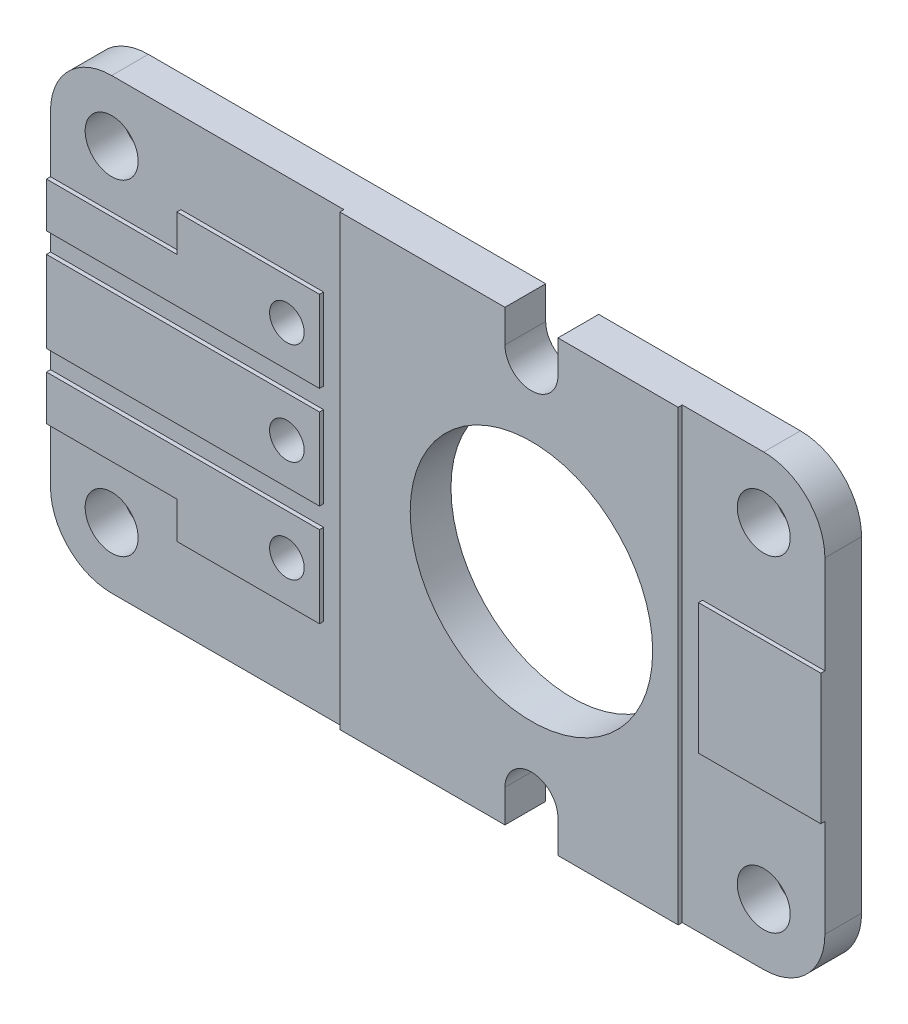
SolidWorks part; units mm, degrees
ref_plane "Спереди" through (0, 0, 0) normal (0, 0, 1) x (1, 0, 0)
ref_plane "Сверху" through (0, 0, 0) normal (0, 1, 0) x (1, 0, 0)
ref_plane "Справа" through (0, 0, 0) normal (1, 0, 0) x (0, 0, -1)
sketch "Model" plane through (0, 0, 0) normal (0, 0, 1) x (1, 0, 0)
  line L0 (1025.0386, -772.2) -> (1025.0386, -762.8) construction
  line L1 (1024.3886, -762.8) -> (1024.3886, -762)
  line L2 (1025.0386, -763.5) -> (1030.6386, -763.5) construction
  line L3 (1025.6886, -762.8) -> (1025.6886, -762)
  line L4 (1025.0386, -763.5) -> (1014.6386, -763.5) construction
  line L5 (1013.1386, -763.5) -> (1013.1386, -771.5)
  line L6 (1025.0386, -767.5) -> (1032.9639, -767.5) construction
  line L7 (1032.1386, -763.5) -> (1032.1386, -771.5)
  line L8 (1014.6386, -762) -> (1030.6386, -762)
  line L9 (1014.6386, -773) -> (1030.6386, -773)
  line L10 (1025.0386, -771.5) -> (1014.6386, -771.5) construction
  line L11 (1025.0386, -771.5) -> (1030.6386, -771.5) construction
  line L12 (1024.3886, -762.8) -> (1024.3886, -762)
  line L13 (1025.6886, -762.8) -> (1025.6886, -762)
  line L14 (1025.6886, -772.2) -> (1025.6886, -773)
  line L15 (1024.3886, -772.2) -> (1024.3886, -773)
  line L16 (1025.6886, -772.2) -> (1025.6886, -773)
  line L17 (1024.3886, -772.2) -> (1024.3886, -773)
  arc A0 (1024.3886, -762.8) -> (1025.6886, -762.8) centre (1025.0386, -762.8) ccw
  arc A1 (1025.0386, -770.5001) -> (1025.0386, -764.5) centre (1025.0386, -767.5001) ccw
  arc A2 (1025.0386, -764.5) -> (1025.0386, -770.5001) centre (1025.0386, -767.5001) ccw
  circle A12 centre (1014.6386, -763.5) radius 1.5
  circle A13 centre (1030.6386, -763.5) radius 1.5
  circle A14 centre (1014.6386, -763.5) radius 0.65
  circle A15 centre (1030.6386, -763.5) radius 0.65
  circle A16 centre (1014.6386, -771.5) radius 0.65
  circle A17 centre (1014.6386, -771.5) radius 1.5
  circle A18 centre (1019.0386, -765) radius 0.4246
  circle A19 centre (1019.0386, -765) radius 0.7246
  circle A20 centre (1019.0378, -767.4991) radius 0.4246
  circle A21 centre (1019.0378, -767.4991) radius 0.7246
  circle A22 centre (1019.0386, -770) radius 0.4246
  circle A23 centre (1019.0386, -770) radius 0.7246
  circle A24 centre (1025.0386, -767.5) radius 2.9746
  circle A25 centre (1025.0386, -767.5) radius 3.4746
  circle A26 centre (1030.6386, -771.5) radius 0.65
  circle A27 centre (1030.6386, -771.5) radius 1.5
  arc A28 (1024.3886, -772.2) -> (1025.6886, -772.2) centre (1025.0386, -772.2) cw
  point P27 (1013.1386, -767.5)
  point P45 (1032.1386, -767.5)
  dimension "D1" = 9.4
  dimension "D2" = 4
  dimension "D3" = 4
extrude "Бобышка-Вытянуть1" add sketch "Model" along normal mid plane 1 contours A25 A23 A21 A19 | A25 A2 A1 | A1 A2 A24 | A23 A22 | A21 A20 | A19 A18 | A27 A26 | A13 A15 | A12 A14 | A17 A16 region at (1025.0386, -763.6696, 0) region at (1015.6693, -762.4694, 0) region at (1031.6693, -762.4694, 0) region at (1014.6386, -770.0425, 0) region at (1031.6693, -772.5307, 0) region at (1022.047, -767.5001, 0) region at (1018.3345, -765, 0) region at (1018.3337, -767.4991, 0) region at (1018.3345, -770, 0) region at (1021.6623, -767.5, 0)
sketch "Эскиз2" plane through (0, 0, 0.5) normal (0, 0, 1) x (1, 0, 0)
  line L2 (1029.2386, -760.837) -> (1034.3761, -760.837)
  line L3 (1034.3761, -760.837) -> (1034.3761, -770.1)
  line L4 (1025.0386, -767.5) -> (1032.1386, -767.5)
  line L5 (1034.3761, -774.163) -> (1034.3761, -770.1)
  line L6 (1029.2386, -774.163) -> (1034.3761, -774.163)
  line L9 (1014.6386, -764.9) -> (1011.6405, -764.9)
  line L10 (1016.0386, -760.614) -> (1011.6405, -760.614)
  line L11 (1011.6405, -760.614) -> (1011.6405, -764.9)
  line L12 (1019.8386, -766) -> (1019.8386, -764)
  line L13 (1019.8386, -760.837) -> (1020.3386, -760.837)
  line L14 (1020.3386, -760.837) -> (1020.3386, -764)
  line L15 (1019.8386, -760.837) -> (1016.0386, -760.614)
  line L16 (1016.3386, -766.5) -> (1011.6405, -766.5)
  line L17 (1011.6405, -766.5) -> (1011.6405, -766)
  line L18 (1011.6405, -766) -> (1016.3386, -766)
  line L19 (1011.6405, -769) -> (1016.3386, -769)
  line L20 (1011.6405, -768.5) -> (1011.6405, -769)
  line L21 (1016.3386, -768.5) -> (1011.6405, -768.5)
  line L22 (1032.1386, -763.5) -> (1032.1386, -771.5) construction
  line L23 (1016.3386, -766) -> (1019.8386, -766)
  line L24 (1020.3386, -766) -> (1020.3386, -769)
  line L25 (1019.8386, -769) -> (1016.3386, -769)
  line L26 (1016.3386, -766.5) -> (1019.8386, -766.5)
  line L27 (1019.8386, -766.5) -> (1019.8386, -768.5)
  line L28 (1019.8386, -768.5) -> (1016.3386, -768.5)
  line L29 (1014.6386, -764.9) -> (1016.3386, -764.9)
  line L30 (1016.3386, -764.9) -> (1016.3386, -764)
  line L31 (1016.3386, -764) -> (1019.8386, -764)
  line L32 (1020.3386, -764) -> (1020.3386, -766)
  line L33 (1020.3386, -771) -> (1020.3386, -769)
  line L34 (1016.3386, -771) -> (1019.8386, -771)
  line L35 (1016.3386, -770.1) -> (1016.3386, -771)
  line L36 (1014.6386, -770.1) -> (1016.3386, -770.1)
  line L37 (1016.3386, -769) -> (1019.8386, -769)
  line L38 (1011.6405, -769) -> (1016.3386, -769)
  line L39 (1019.8386, -774.163) -> (1016.0386, -774.3861)
  line L40 (1020.3386, -774.163) -> (1020.3386, -771)
  line L41 (1019.8386, -774.163) -> (1020.3386, -774.163)
  line L42 (1019.8386, -769) -> (1019.8386, -771)
  line L43 (1011.6405, -774.3861) -> (1011.6405, -770.1)
  line L44 (1016.0386, -774.3861) -> (1011.6405, -774.3861)
  line L45 (1014.6386, -770.1) -> (1011.6405, -770.1)
  line L46 (1032.1386, -769.1) -> (1032.1386, -765.9)
  line L47 (1032.1386, -765.9) -> (1029.1386, -765.9)
  line L48 (1029.1386, -765.9) -> (1029.1386, -769.1)
  line L49 (1032.1386, -769.1) -> (1029.1386, -769.1)
  line L50 (1029.1386, -767.5) -> (1028.6386, -767.5)
  line L51 (1028.6386, -767.5) -> (1028.6386, -760.837)
  line L52 (1028.6386, -767.5) -> (1028.6386, -774.163)
  line L53 (1028.6386, -774.163) -> (1029.2386, -774.163)
  line L54 (1028.6386, -760.837) -> (1029.2386, -760.837)
  line L55 (1032.1386, -769.1) -> (1032.1386, -765.9)
  point P55 (1029.1386, -767.5)
  line M14 (1025.6886, -773) -> (1030.6386, -773)
  arc M15 (1030.6386, -773) -> (1032.1386, -771.5) centre (1030.6386, -771.5) ccw
  line M16 (1032.1386, -771.5) -> (1032.1386, -763.5)
  arc M17 (1032.1386, -763.5) -> (1030.6386, -762) centre (1030.6386, -763.5) ccw
  line M18 (1030.6386, -762) -> (1025.6886, -762)
  line M22 (1024.3886, -762) -> (1014.6386, -762)
  arc M23 (1014.6386, -762) -> (1013.1386, -763.5) centre (1014.6386, -763.5) ccw
  line M24 (1013.1386, -763.5) -> (1013.1386, -771.5)
  arc M25 (1013.1386, -771.5) -> (1014.6386, -773) centre (1014.6386, -771.5) ccw
  line M26 (1014.6386, -773) -> (1024.3886, -773)
  circle M27 centre (1014.6386, -771.5) radius 0.65
  circle M28 centre (1014.6386, -763.5) radius 0.65
  circle M29 centre (1030.6386, -763.5) radius 0.65
  circle M30 centre (1030.6386, -771.5) radius 0.65
extrude "Вырез-Вытянуть1" cut sketch "Эскиз2" against normal blind 0.1 contours L36 L45 L40 L33 L24 L32 L14 L9 L29 L30 L31 L12 L23 L18 L16 L26 L27 L28 L21 L19 L25 L42 L34 L35 M24 M25 M26 M22 M23 M27 M28 | M16 M17 M18 M29 | M14 M15 M16 M30 region at (1030.2133, -764.233, 0.5) region at (1030.2133, -770.767, 0.5) region at (1013.8886, -764.7686, 0.5)
